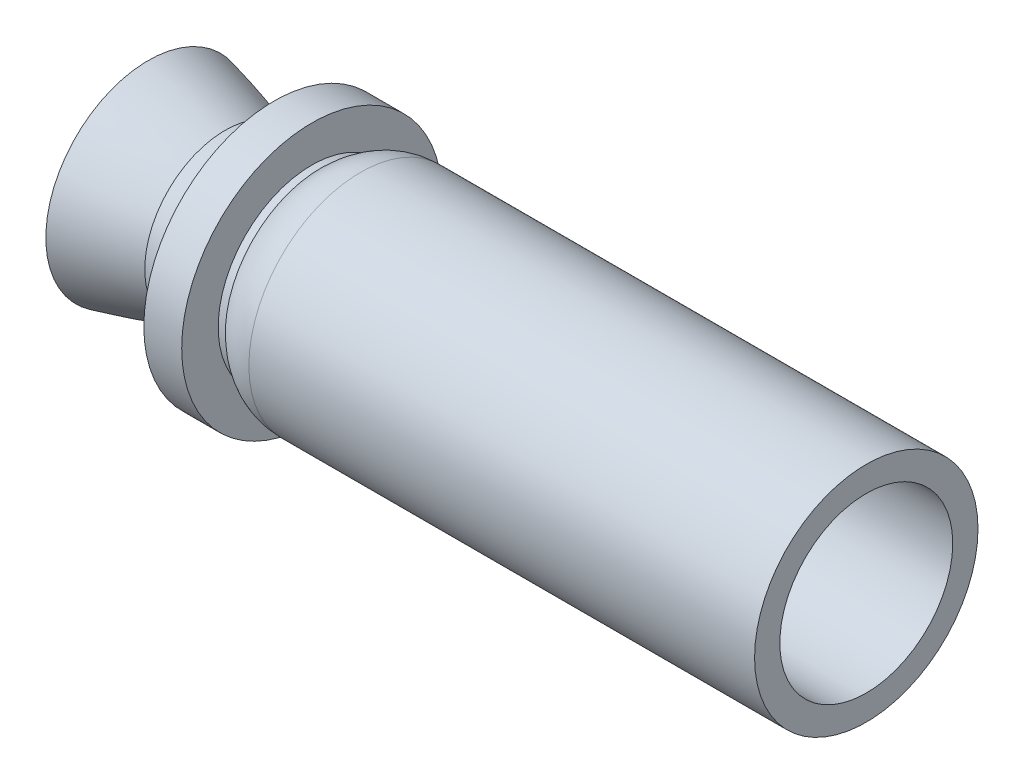
SolidWorks part; units mm, degrees
material "Thornel Mat VMA"
ref_plane "Front Plane" through (0, 0, 0) normal (0, 0, 1) x (1, 0, 0)
ref_plane "Top Plane" through (0, 0, 0) normal (0, 1, 0) x (1, 0, 0)
ref_plane "Right Plane" through (0, 0, 0) normal (1, 0, 0) x (0, 0, -1)
sketch "Sketch1" plane through (0, 0, 0) normal (0, 0, 1) x (1, 0, 0)
  line L0 (189.133, 27.386) -> (28.9492, 27.386)
  line L1 (21.8782, 24.4571) -> (13.5417, 16.1206)
  line L3 (0, 0) -> (-234.9488, 0) construction
  line L5 (16.2213, 30.1139) -> (-13.9816, 25.4377)
  line L8 (189.133, 35.386) -> (28.9492, 35.386)
  line L12 (16.2213, 30.1139) -> (7.8848, 21.7775)
  line L13 (189.133, 27.386) -> (189.133, 35.386)
  line L14 (-40.127, 24.64) -> (-38.315, 32.4321)
  arc A0 (28.9492, 27.386) -> (21.8782, 24.4571) centre (28.9492, 17.386) ccw
  arc A4 (28.9492, 35.386) -> (16.2213, 30.1139) centre (28.9492, 17.386) ccw
  arc A7 (2.3482, 19.2268) -> (2.3482, 19.2268) centre (2.3482, 19.2268) cw
  arc A8 (7.8848, 21.7775) -> (2.3482, 19.2268) centre (1.6623, 28) cw construction
  arc A9 (2.3482, 19.2268) -> (7.8848, 21.7775) centre (1.6623, 28) ccw
  arc A10 (0.1069, 11.2722) -> (0, 11.5361) centre (3.1693, 12.6659) cw construction
  arc A11 (13.5417, 16.1206) -> (0.1069, 11.2722) centre (1.6623, 28) cw construction
  arc A12 (13.5417, 16.1206) -> (1.6623, 11.2) centre (1.6623, 28) cw
  arc A13 (1.6623, 11.2) -> (0, 11.5361) centre (1.6623, 15.4784) cw
  spline S0 degree 2 poles (0, 11.5361) (-19.9483, 19.9476) (-40.127, 24.64) knots 0 0 0 1 1 1 construction
  spline S1 degree 1 poles (2.3482, 19.2268) (-38.315, 32.4321) knots 0 0 1 1 construction
  spline S2 degree 2 poles (0, 11.5361) (-19.9483, 19.9476) (-40.127, 24.64) knots 0 0 0 1 1 1
  spline S3 degree 2 poles (2.3482, 19.2268) (0.3135, 20.0775) (-5.8003, 22.5182) (-13.9784, 25.475) (-28.1602, 30.0701) (-38.315, 32.4321) knots 0.018494 0.018494 0.018494 0.117488 0.315475 0.513463 1 1 1
  dimension "D1" = 10
  dimension "D4" = 16.8
  dimension "D5" = 4.2784
  dimension "D14" = 27.386
  dimension "D16" = 167.2548
  dimension "D2" = 11.2
  dimension "D6" = 45
  dimension "D7" = 24.64
  dimension "D3" = 8
revolve "Revolve1" add sketch "Sketch1" angle 360 about L3 region at (72.719, 28.6368, 0) region at (2.2964, 24.7796, 0)
ref_plane "Plane1" through (0, 0, 40) normal (0, 0, 1) x (1, 0, 0)
sketch "Sketch2" plane through (0, 0, 40) normal (0, 0, 1) x (1, 0, 0)
  line L0 (-13.9816, 25.4377) -> (-13.9816, -25.4377) construction
  line L2 (16.2213, -30.1139) -> (16.2213, 30.1139) construction
  line L3 (-13.9816, 25.4377) -> (-13.9816, -25.4377) construction
  line L4 (-13.9816, 0) -> (16.2213, 0) construction
  line L6 (1.6623, 11.2) -> (1.6623, -11.2) construction
  circle A0 centre (1.6623, 0) radius 2.5
  dimension "D2" = 5
sketch "Sketch3" plane through (0, 0, 0) normal (0, 0, 1) x (1, 0, 0)
  line L0 (16.2213, 30.1139) -> (7.8848, 21.7775) construction
  line L1 (16.2213, 30.1139) -> (7.8848, 21.7775)
  line L2 (1.5417, 15.4343) -> (1.5417, 41.25)
  line L3 (1.5417, 41.25) -> (13.5417, 41.25)
  line L4 (13.5417, 16.1206) -> (13.5417, 41.25)
  line L5 (189.133, 35.386) -> (28.9492, 35.386) construction
  line L6 (200000, 0) -> (-200234.9488, 0) construction
  line L7 (28.9492, 35.386) -> (28.9492, -35.386) construction
  line L8 (28.9492, 35.386) -> (28.9492, -35.386)
  line L9 (189.133, 35.386) -> (28.9492, 35.386)
  line L10 (21.8782, 24.4571) -> (21.8782, -24.4571) construction
  line L11 (21.8782, 24.4571) -> (21.8782, -24.4571)
  line L12 (21.8782, 24.4571) -> (22.0609, 34.0158)
  line L14 (13.5417, 16.1206) -> (13.5417, -16.1206) construction
  line L15 (13.5417, 16.1206) -> (13.5417, -16.1206)
  arc A0 (2.3482, 19.2268) -> (7.8848, 21.7775) centre (1.6623, 28) ccw construction
  arc A1 (2.3482, 19.2268) -> (7.8848, 21.7775) centre (1.6623, 28) ccw
  arc A2 (28.9492, 35.386) -> (16.2213, 30.1139) centre (28.9492, 17.386) ccw construction
  arc A3 (28.9492, 35.386) -> (16.2213, 30.1139) centre (28.9492, 17.386) ccw
  spline S0 degree 2 poles (688.9163, -1836.1468) (411.4133, -144.0397) (-5.8003, 22.5182) (-13.9784, 25.475) (-484.9314, 178.0717) (-1112.4109, -1610.0203) knots -19.950852 -19.950852 -19.950852 0.117488 0.315475 0.513463 23.047357 23.047357 23.047357 only from (2.3482, 19.2268) to (-38.315, 32.4321) construction
  spline S1 degree 2 poles (2.3482, 19.2268) (0.3135, 20.0775) (-5.8003, 22.5182) (-13.9784, 25.475) (-28.1602, 30.0701) (-38.315, 32.4321) knots 0.018494 0.018494 0.018494 0.117488 0.315475 0.513463 1 1 1
  point P9 (1.6623, 15.4343)
  dimension "D1" = 12
  dimension "D2" = 41.25
  dimension "D3" = 12
revolve "Revolve2" add sketch "Sketch3" angle 360 about L3 region at (7.0812, 31.5351, 0)
split "Split1" bodies to split 106 resulting bodies 107 108 split by face at (13.5417, 0, -29.699)
equation "\"theta_t\"= 36.9009 - ( 426.271 / ( \"Aet\" + 7.00037 ) ) + ( 10026.8 / ( \"Aet\" + 7.00037 ) ^ 2 ) - ( 175410 / ( \"Aet\" + 7.00037 ) ^ 3 ) + ( ( 1.6742 * ( 10 ^ 6 ) ) / ( \"Aet\" + 7.00037 ) ^ 4 ) - ( ( 6.7643 * ( 10 ^ 6 ) ) / ( \"Aet\" + 7.00037 ) ^ 5 )"
equation "\"rt\"= 11.2"
equation "\"re\"= sqr ( \"rt\" ^ 2 * \"Aet\" )"
equation "\"Aet\"= 4.84"
equation "\"L\"= 0.8 * ( ( \"re\" / tan ( 15 ) ) - ( \"rt\" / tan ( 15 ) ) )"
equation "\"lc\"= ( \"l*\" / \"cr\" )"
equation "\"b\"= tan ( \"theta_t\" )"
equation "\"a\"= ( \"re\" - \"b\" * \"L\" - \"c\" ) / \"L\" ^ 2"
equation "\"c\"= \"rt\" * ( 1.382 - 0.382 * cos ( \"theta_t\" ) )"
equation "\"cr\"= 5.9789"
equation "\"rc\"= sqr ( \"cr\" * ( \"rt\" ^ 2 ) )"
equation "\"D14@Sketch1\"=\"rc\""
equation "\"l*\"= 1000"
equation "\"D16@Sketch1\"=\"lc\""
equation "\"th\"= 8"
equation "\"theta_cr\"= 45deg"
equation "\"theta_e\"= 5.48 + ( 134.316 / ( \"Aet\" + 1.49269 ) ) - ( 1742.02 / ( \"Aet\" + 1.49269 ) ^ 2 ) + ( 13091 / ( \"Aet\" + 1.49269 ) ^ 3 ) - ( 41929.9 / ( \"Aet\" + 1.49269 ) ^ 4 ) + ( 44445.1 / ( \"Aet\" + 1.49269 ) ^ 5 )"
equation "\"Nx\"= 0"
equation "\"Ny\"= \"c\""
equation "\"Qx\"= ( \"re\" - ( tan ( \"theta_e\" ) * \"L\" ) - \"c\" ) / ( tan ( \"theta_t\" ) - tan ( \"theta_e\" ) )"
equation "\"Qy\"= tan ( \"theta_t\" ) * \"Qx\" + \"c\""
equation "\"Ex\"= \"L\""
equation "\"Ey\"= \"re\""
equation "\"D3@Sketch1\"=\"th\""
equation "\"D2@Sketch1\"=\"rt\""
equation "\"D4@Sketch1\"=\"rt\"*1.5"
equation "\"D5@Sketch1\"=\"rt\"*0.382"
equation "\"D6@Sketch1\"=\"theta_cr\""
equation "\"D7@Sketch1\"=\"re\""
equation "\"D2@Sketch3\"=(88.9)/2 -3.2"
